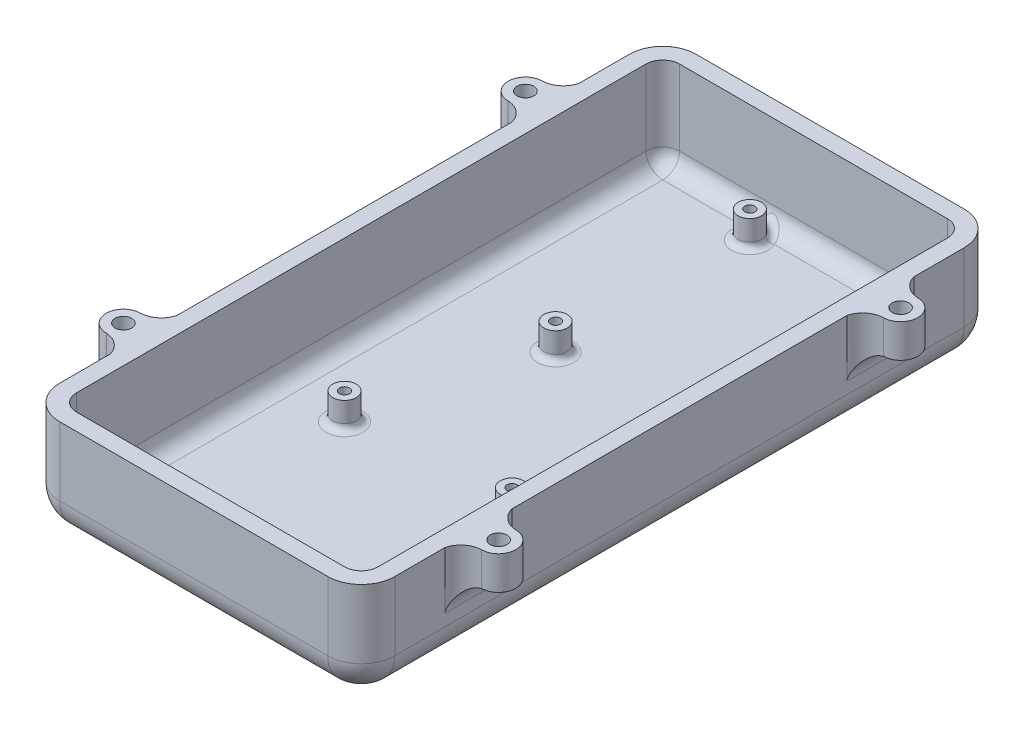
SolidWorks part; units mm, degrees
ref_plane "前视基准面" through (0, 0, 0) normal (0, 0, 1) x (1, 0, 0)
ref_plane "上视基准面" through (0, 0, 0) normal (0, 1, 0) x (1, 0, 0)
ref_plane "右视基准面" through (0, 0, 0) normal (1, 0, 0) x (0, 0, -1)
sketch "Sketch1" plane through (0, 0, 0) normal (0, 1, 0) x (1, 0, 0)
  line L0 (-50, -95) -> (-50, 95)
  line L1 (-45, -90) -> (45, -90)
  line L2 (-45, -90) -> (-45, 90)
  line L3 (-45, 90) -> (45, 90)
  line L4 (45, -90) -> (45, 90)
  line L5 (-45, -90) -> (45, 90) construction
  line L6 (-45, 90) -> (45, -90) construction
  line L7 (-50, 95) -> (50, 95)
  line L8 (50, -95) -> (50, 95)
  line L9 (-50, -95) -> (50, -95)
  point P0 (0, 0)
  dimension "D1" = 90
  dimension "D2" = 180
  dimension "D3" = 5
extrude "Boss-Extrude1" add sketch "Sketch1" along normal blind 27.5
sketch3d "3DSketch1"
  line L4 (50, 0, 95) -> (-50, 0, 95)
  line L5 (-50, 0, 95) -> (-50, 0, -95)
  line L6 (-50, 0, -95) -> (50, 0, -95)
  line L7 (50, 0, -95) -> (50, 0, 95)
  line L8 (50, 0, 95) -> (-50, 0, 95)
  line L9 (-50, 0, 95) -> (-50, 0, -95)
  line L10 (-50, 0, -95) -> (50, 0, -95)
  line L11 (50, 0, -95) -> (50, 0, 95)
  dimension "D1" = 0
extrude "Boss-Extrude2" add sketch "3DSketch1" along direction (0, 1, 0) on the side of the normal blind 3
fillet "Fillet3" radius 10 4 edges
fillet "Fillet4" radius 10 8 edges at (-47.0711, -3, 92.0711) (47.0711, -3, 92.0711) (47.0711, -3, -92.0711) (-47.0711, -3, -92.0711)
fillet "Fillet5" radius 5 4 edges at (45, 13.75, 90) (45, 13.75, -90) (-45, 13.75, -90) (-45, 13.75, 90)
fillet "Fillet6" radius 5 8 edges at (-43.5355, 0, 88.5355) (-45, 0, 0) (-43.5355, 0, -88.5355) (0, 0, -90) (43.5355, 0, -88.5355) (45, 0, 0) (43.5355, 0, 88.5355) (0, 0, 90)
sketch "Sketch2" plane through (0, 27.5, 0) normal (0, 1, 0) x (1, 0, 0)
  line L0 (-50, 0) -> (-50, 60) construction
  line L1 (-50, 85) -> (-50, -85) construction
  line L2 (-50, 60) -> (-56, 60) construction
  line L4 (-56, 60) -> (-61.5, 60) construction
  line L5 (0, 0) -> (0, 13.0765) construction
  line L6 (0, 0) -> (12.355, 0) construction
  line L10 (-50, 50) -> (-50, 70)
  line L11 (50, 50) -> (50, 70)
  line L12 (50, -50) -> (50, -70)
  line L13 (-50, -50) -> (-50, -70)
  arc A0 (-56, 65.1284) -> (-56, 54.8716) centre (-56, 60) ccw
  circle A4 centre (-56, 60) radius 2.5
  arc A17 (-56, 65.1284) -> (-50, 70) centre (-56.2944, 71.6217) ccw
  arc A18 (-56, 54.8716) -> (-50, 50) centre (-56.2944, 48.3783) cw
  circle A19 centre (56, 60) radius 2.5
  arc A20 (56, 54.8716) -> (50, 50) centre (56.2944, 48.3783) ccw
  arc A21 (56, 65.1284) -> (56, 54.8716) centre (56, 60) cw
  arc A22 (56, 65.1284) -> (50, 70) centre (56.2944, 71.6217) cw
  circle A23 centre (56, -60) radius 2.5
  arc A24 (56, -65.1284) -> (56, -54.8716) centre (56, -60) ccw
  arc A25 (56, -65.1284) -> (50, -70) centre (56.2944, -71.6217) ccw
  arc A26 (56, -54.8716) -> (50, -50) centre (56.2944, -48.3783) cw
  circle A27 centre (-56, -60) radius 2.5
  arc A28 (-56, -54.8716) -> (-50, -50) centre (-56.2944, -48.3783) ccw
  arc A29 (-56, -65.1284) -> (-56, -54.8716) centre (-56, -60) cw
  arc A30 (-56, -65.1284) -> (-50, -70) centre (-56.2944, -71.6217) cw
  dimension "D1" = 6
  dimension "D3" = 5
  dimension "D2" = 60
  dimension "D4" = 10
extrude "Boss-Extrude3" add sketch "Sketch2" against normal blind 10
fillet "Fillet7" radius 7 4 edges at (-50, 17.5, -60) (50, 17.5, -60) (50, 17.5, 60) (-50, 17.5, 60)
sketch "Sketch3" plane through (0, 17.5, 0) normal (0, -1, 0) x (1, 0, 0)
  circle A0 centre (-56, -60) radius 5.1284
  circle A1 centre (-56, 60) radius 5.1284
  circle A2 centre (56, 60) radius 5.1284
  circle A3 centre (56, -60) radius 5.1284
extrude "Cut-Extrude1" cut sketch "Sketch3" along normal blind 10
sketch "Sketch5" plane through (0, 0, 0) normal (0, 1, 0) x (1, 0, 0)
  line L0 (0, 0) -> (0, -50) construction
  line L1 (0, -50) -> (20.9359, -50) construction
  line L2 (25, -25) -> (-25, -25) construction
  line L3 (25, -25) -> (25, -75) construction
  line L4 (25, -75) -> (-25, -75) construction
  line L5 (-25, -25) -> (-25, -75) construction
  line L6 (25, -25) -> (-25, -75) construction
  line L7 (25, -75) -> (-25, -25) construction
  circle A0 centre (25, -75) radius 3.5
  circle A1 centre (25, -75) radius 1.5
  circle A2 centre (-25, -75) radius 1.5
  circle A3 centre (-25, -75) radius 3.5
  circle A4 centre (-25, -25) radius 1.5
  circle A5 centre (-25, -25) radius 3.5
  circle A6 centre (25, -25) radius 1.5
  circle A7 centre (25, -25) radius 3.5
  dimension "D4" = 7
  dimension "D5" = 3
  dimension "D1" = 50
  dimension "D2" = 50
  dimension "D3" = 50
extrude "Boss-Extrude4" add sketch "Sketch5" along normal blind 8
ref_plane "Plane4" through (0, 0, 75) normal (0, 0, -1) x (-1, 0, 0)
sketch "Sketch14" plane through (0, 0, 0) normal (0, 1, 0) x (1, 0, 0)
  line L0 (0, 0) -> (0, -85) construction
  line L1 (-40, -85) -> (40, -85) construction
ref_plane "Plane5" through (0, 0, 0) normal (1, 0, 0) x (0, 0, -1)
sketch "Sketch15" plane through (0, 0, 0) normal (0, 1, 0) x (1, 0, 0)
  line L0 (-25, -75) -> (-25, -25) construction
  line L1 (-25, -50) -> (5.5244, -50) construction
ref_plane "Plane6" through (0, 0, 50) normal (0, 0, -1) x (-1, 0, 0)
sketch "Sketch17" plane through (0, 0, 0) normal (0, 1, 0) x (1, 0, 0)
  circle A0 centre (37.5, 24.5) radius 1.5
  circle A1 centre (37.5, 24.5) radius 3.5
  circle A2 centre (-11.5, 24.5) radius 1.5
  circle A3 centre (-11.5, 24.5) radius 3.5
  circle A4 centre (37.5, 82.5) radius 1.5
  circle A5 centre (37.5, 82.5) radius 3.5
  circle A6 centre (-11.5, 82.5) radius 1.5
  circle A7 centre (-11.5, 82.5) radius 3.5
  dimension "D1" = 3
  dimension "D2" = 7
  dimension "D3" = 7
  dimension "D4" = 3
  dimension "D5" = 7
  dimension "D6" = 3
  dimension "D7" = 7
  dimension "D8" = 3
extrude "Boss-Extrude7" add sketch "Sketch17" along normal blind 8
fillet "Fillet9" radius 1.9 9 edges at (-10.5227, 0.0747, -85.8608) (37.8662, 0.0971, -85.9808) (39.9749, 0, -84.9749) (40.8608, 0.0747, -81.5227) (40.8608, 0.0747, -23.5227) (-11.5, 0, -79) (35.0251, 0, -80.0251) (34, 0, -24.5) (-11.5, 0, -21)
fillet "Fillet10" radius 2 4 edges at (25, 0, 21.5) (-25, 0, 28.5) (-25, 0, 71.5) (25, 0, 78.5)
